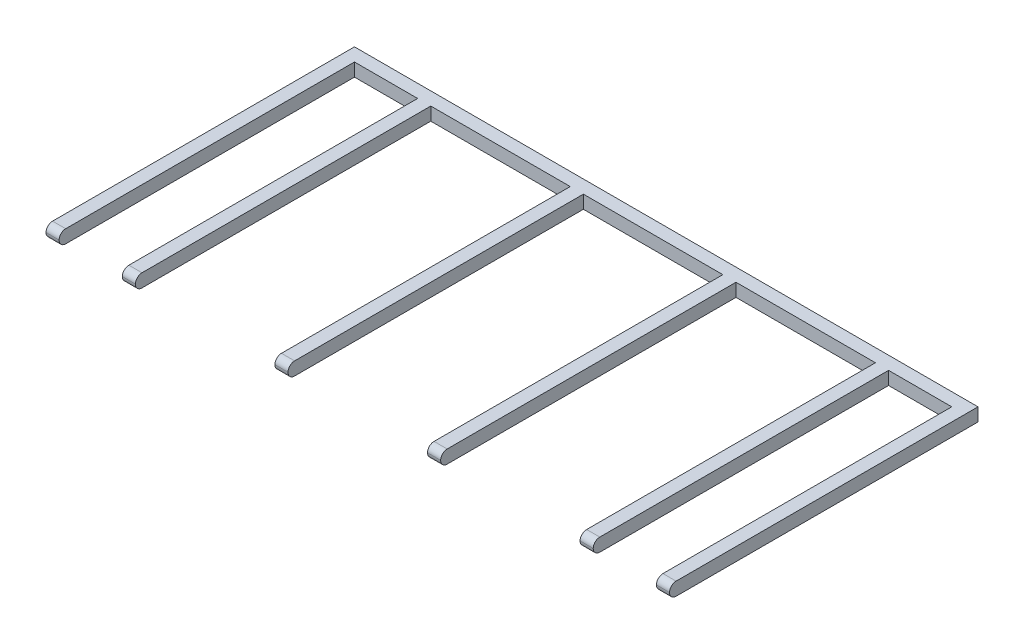
SolidWorks part; units mm, degrees
material "Cast Carbon Steel"
ref_plane "Front Plane" through (0, 0, 0) normal (0, 0, 1) x (1, 0, 0)
ref_plane "Top Plane" through (0, 0, 0) normal (0, 1, 0) x (1, 0, 0)
ref_plane "Right Plane" through (0, 0, 0) normal (1, 0, 0) x (0, 0, -1)
sketch "Sketch1" plane through (0, 0, 0) normal (1, 0, 0) x (0, 0, -1)
  line L1 (2.54, -2.54) -> (-2.54, -2.54)
  line L2 (2.54, -2.54) -> (2.54, 2.54)
  line L3 (2.54, 2.54) -> (-2.54, 2.54)
  line L4 (-2.54, -2.54) -> (-2.54, 2.54)
  line L5 (2.54, -2.54) -> (-2.54, 2.54) construction
  line L6 (2.54, 2.54) -> (-2.54, -2.54) construction
  point P0 (0, 0)
  dimension "D1" = 5.08
extrude "Boss-Extrude1" add sketch "Sketch1" along normal blind 241.3
sketch "Sketch2" plane through (0, 0, 0) normal (0, 0, 1) x (1, 0, 0)
  line L2 (241.3, -2.54) -> (0, -2.54) construction
  line L3 (0, 2.54) -> (5.08, 2.54)
  line L4 (0, 2.54) -> (0, -2.54)
  line L5 (0, -2.54) -> (5.08, -2.54)
  line L6 (5.08, 2.54) -> (5.08, -2.54)
extrude "Boss-Extrude2" add sketch "Sketch2" along normal blind 116.84
fillet "Fillet1" radius 2.54 2 edges at (2.54, -2.54, 116.84) (2.54, 2.54, 116.84)
pattern_linear "LPattern1" count 9 spacing 29.5275 along (1, 0, 0) skipping (2, 0), (4, 0), (6, 0) of "Boss-Extrude2", "Fillet1"
